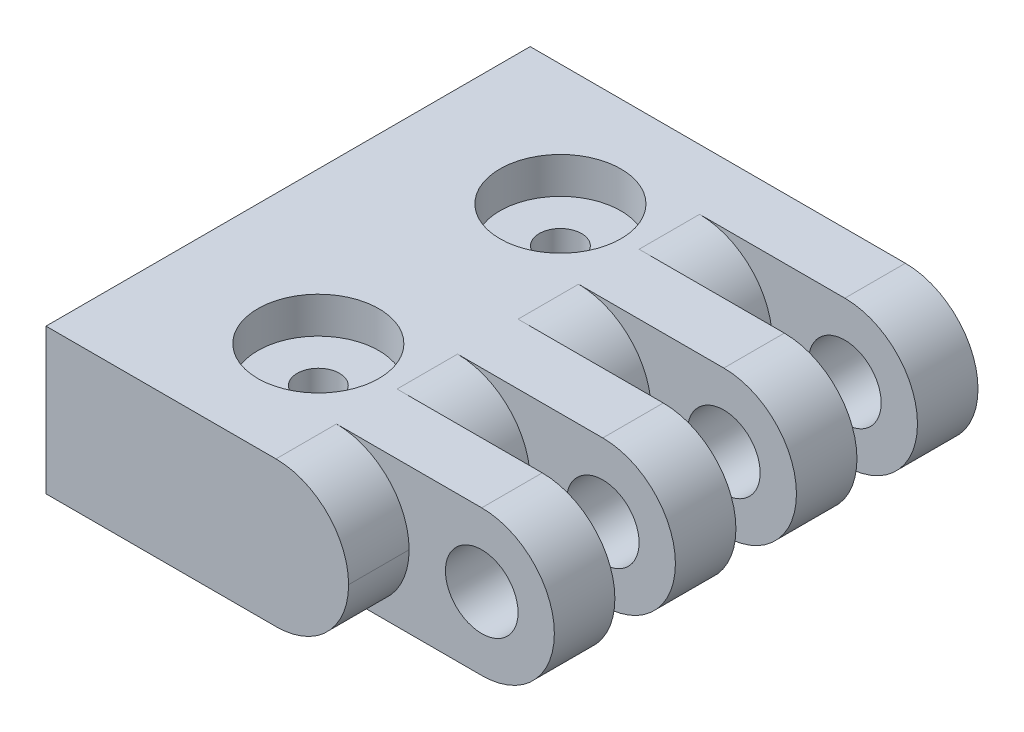
SolidWorks part; units mm, degrees
ref_plane "Front" through (0, 0, 0) normal (0, 0, 1) x (1, 0, 0)
ref_plane "Top" through (0, 0, 0) normal (0, 1, 0) x (1, 0, 0)
ref_plane "Right" through (0, 0, 0) normal (1, 0, 0) x (0, 0, -1)
sketch "Sketch1" plane through (0, 0, 0) normal (0, 1, 0) x (1, 0, 0)
  line L1 (0, 0) -> (-25, 0)
  line L2 (0, 0) -> (0, 40)
  line L3 (0, 40) -> (-25, 40)
  line L4 (-25, 0) -> (-25, 40)
  dimension "D1" = 40
  dimension "D2" = 25
extrude "Boss-Extrude1" add sketch "Sketch1" along normal blind 12
sketch "Sketch2" plane through (0, 0, 0) normal (0, 0, 1) x (1, 0, 0)
  line L0 (0, 0) -> (13.9056, 0) construction
  line L1 (0, 12) -> (0, 0) construction
  line L2 (0, 6) -> (0, 0)
  line L3 (0, 0) -> (6, 0)
  line L4 (0, 6) -> (0, 12)
  line L5 (0, 12) -> (6, 12)
  arc A0 (6, 0) -> (6, 12) centre (6, 6) ccw
  circle A1 centre (6, 6) radius 3
  dimension "D1" = 12
  dimension "D2" = 6
extrude "Boss-Extrude2" add sketch "Sketch2" against normal up to surface (40 mm away) up to face at (-12.5, 6, -40)
sketch "Sketch3" plane through (0, 12, 0) normal (0, 1, 0) x (1, 0, 0)
  line L1 (0, 35) -> (12, 35)
  line L2 (0, 35) -> (0, 30)
  line L3 (0, 30) -> (12, 30)
  line L4 (12, 35) -> (12, 30)
  line L5 (12, 0) -> (12, 40) construction
  line L6 (6, 40) -> (-25, 40) construction
  dimension "D1" = 12
  dimension "D2" = 5
  dimension "7.5" = 5
extrude "Cut-Extrude1" cut sketch "Sketch3" against normal through all
pattern_linear "LPattern1" count 4 spacing 10 along (0, 0, 1) of "Cut-Extrude1"
sketch "Sketch4" plane through (0, 12, 0) normal (0, 1, 0) x (1, 0, 0)
  line L1 (6, 40) -> (-25, 40) construction
  line L2 (-25, 0) -> (0, 0) construction
  line L3 (-12.5, 0) -> (-12.5, 30) construction
  circle A0 centre (-12.5, 30) radius 1.75
  circle A1 centre (-12.5, 10) radius 1.75
  dimension "D4" = 3.5
  dimension "D2" = 10
  dimension "D3" = 10
extrude "Cut-Extrude2" cut sketch "Sketch4" against normal through all
sketch "Sketch5" plane through (0, 12, 0) normal (0, 1, 0) x (1, 0, 0)
  circle A0 centre (-12.5, 30) radius 5
  circle A1 centre (-12.5, 10) radius 5
  dimension "D1" = 10
extrude "Cut-Extrude3" cut sketch "Sketch5" against normal blind 3
pattern_linear "LPattern2" count 2 spacing 9 along (0, -1, 0) of "Cut-Extrude3"
fillet "Fillet1" radius 6 8 edges at (0, 0, -2.5) (0, 12, -2.5) (0, 0, -12.5) (0, 12, -12.5) (0, 0, -22.5) (0, 12, -22.5) (0, 0, -32.5) (0, 12, -32.5)
